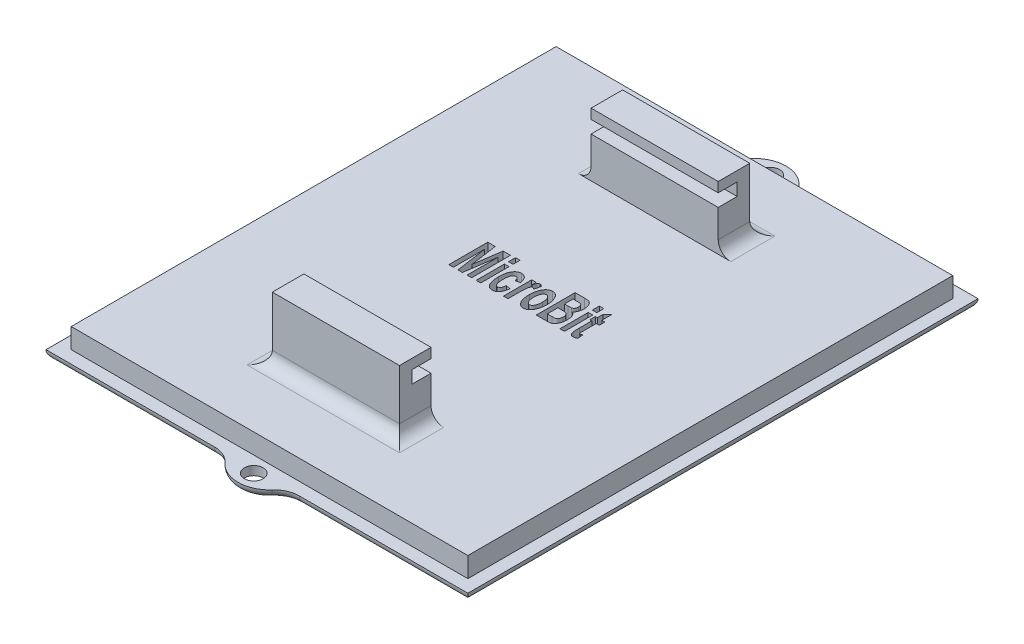
SolidWorks part; units mm, degrees
ref_plane "Front Plane" through (0, 0, 0) normal (0, 0, 1) x (1, 0, 0)
ref_plane "Top Plane" through (0, 0, 0) normal (0, 1, 0) x (1, 0, 0)
ref_plane "Right Plane" through (0, 0, 0) normal (1, 0, 0) x (0, 0, -1)
sketch "Sketch1" plane through (0, 0, 0) normal (0, 1, 0) x (1, 0, 0)
  line L0 (-31.45, 38.45) -> (31.45, 38.45)
  line L5 (-31.45, 38.45) -> (-31.45, -38.45)
  line L6 (-31.45, -38.45) -> (31.45, -38.45)
  line L7 (31.45, 38.45) -> (31.45, -38.45)
  point P11 (-31.45, 0)
  point P12 (0, -38.45)
  dimension "D3" = 76.9
  dimension "D4" = 62.9
extrude "Boss-Extrude1" add sketch "Sketch1" along normal blind 4.575
sketch "Sketch11" plane through (0, 0, 0) normal (0, -1, 0) x (-1, 0, 0)
  line L0 (-31.45, 38.45) -> (31.45, 38.45) construction
  line L1 (-33.45, -40.45) -> (33.45, -40.45)
  line L2 (-33.45, -40.45) -> (-33.45, 40.45)
  line L3 (-33.45, 40.45) -> (33.45, 40.45)
  line L4 (33.45, -40.45) -> (33.45, 40.45)
  line L5 (-31.45, -38.45) -> (-31.45, 38.45) construction
  line L6 (31.45, -38.45) -> (-31.45, -38.45) construction
  line L13 (31.45, 38.45) -> (31.45, -38.45) construction
  dimension "D1" = 2
  dimension "D2" = 2
  dimension "D3" = 2
  dimension "D4" = 2
extrude "Boss-Extrude5" add sketch "Sketch11" against normal blind 1.4
sketch "Sketch4" plane through (0, 0, 0) normal (0, 1, 0) x (1, 0, 0)
  line L2 (-31.45, -38.45) -> (31.45, -38.45) construction
  line L3 (33.45, -40.45) -> (-33.45, -40.45) construction
  line L5 (-6.7082, -40.45) -> (6.7082, -40.45)
  arc A3 (-6.7082, -40.45) -> (-3.7268, -41.7833) centre (-6.7082, -44.45) cw
  arc A4 (-3.7268, -41.7833) -> (3.7268, -41.7833) centre (0, -38.45) ccw
  arc A5 (3.7268, -41.7833) -> (6.7082, -40.45) centre (6.7082, -44.45) cw
  dimension "D1" = 5
  dimension "D4" = 4
extrude "Boss-Extrude3" add sketch "Sketch4" along normal blind 1.4
sketch "Sketch12" plane through (0, 1.4, 0) normal (0, 1, 0) x (1, 0, 0)
  line L0 (0, -38.45) -> (0, -43.45) construction
  line L1 (-31.45, -38.45) -> (31.45, -38.45) construction
  arc A0 (-3.7268, -41.7833) -> (3.7268, -41.7833) centre (0, -38.45) ccw construction
  circle A1 centre (0, -40.95) radius 1.5
  dimension "D1" = 3
extrude "Cut-Extrude3" cut sketch "Sketch12" against normal up to next
mirror "Mirror1" about plane through (0, 0, 0) normal (0, 0, 1) of "Cut-Extrude3", "Boss-Extrude3"
fillet "Fillet1" radius 1.4 12 edges at (20.0791, 0, -40.45) (5.0752, 0, -40.7985) (0, 0, -43.45) (-5.0752, 0, -40.7985) (-20.0791, 0, -40.45) (-33.45, 0, 0) (-20.0791, 0, 40.45) (-5.0752, 0, 40.7985) (0, 0, 43.45) (5.0752, 0, 40.7985) (20.0791, 0, 40.45) (33.45, 0, 0)
sketch "Sketch5" plane through (0, 4.575, 0) normal (0, 1, 0) x (1, 0, 0)
  line L0 (-15, 0) -> (15, 0) construction
  text T0 "MicroBit" font "Arial Narrow" height in points 24
  point P6 (0, 0)
  dimension "D1" = 30
extrude "Letters" cut sketch "Sketch5" against normal blind 2
sketch "Sketch21" plane through (0, 4.575, 0) normal (0, 1, 0) x (1, 0, 0)
  line L1 (-21.1498, 24.9347) -> (20.8502, 24.9347)
  line L2 (-21.1498, 24.9347) -> (-21.1498, -26.5653)
  line L3 (-21.1498, -26.5653) -> (20.8502, -26.5653)
  line L4 (20.8502, 24.9347) -> (20.8502, -26.5653)
  line L5 (-21.1498, 24.9347) -> (20.8502, -26.5653) construction
  line L6 (-21.1498, -26.5653) -> (20.8502, 24.9347) construction
  line L7 (-10.2291, -22.7722) -> (9.9294, -22.7722)
  line L8 (-10.2291, -22.7722) -> (-10.2291, -27.7722)
  line L9 (-10.2291, -27.7722) -> (9.9294, -27.7722)
  line L10 (9.9294, -22.7722) -> (9.9294, -27.7722)
  line L11 (-10.2291, -22.7722) -> (9.9294, -27.7722) construction
  line L12 (-10.2291, -27.7722) -> (9.9294, -22.7722) construction
  point P4 (-0.1498, -0.8153)
  point P9 (-0.1498, -25.2722)
  dimension "D1" = 42
  dimension "D2" = 51.5
  dimension "D3" = 5
extrude "Boss-Extrude8" add sketch "Sketch21" along normal blind 10 contours L9 L10 L7 L8
sketch "Sketch33" plane through (9.9294, 0, 0) normal (1, 0, 0) x (0, 0, -1)
  line L0 (-22.7722, 14.575) -> (-22.7722, 4.575) construction
  line L1 (-22.7722, 13.0159) -> (-25.7722, 13.0159)
  line L2 (-22.7722, 13.0159) -> (-22.7722, 11.0159)
  line L3 (-22.7722, 11.0159) -> (-25.7722, 11.0159)
  line L4 (-25.7722, 13.0159) -> (-25.7722, 11.0159)
  line L5 (-22.7722, 13.0159) -> (-25.7722, 11.0159) construction
  line L6 (-22.7722, 11.0159) -> (-25.7722, 13.0159) construction
  point P4 (-24.2722, 12.0159)
  dimension "D1" = 2
  dimension "D2" = 3
extrude "Cut-Extrude7" cut sketch "Sketch33" against normal blind 25
mirror "Mirror2" about plane through (0, 0, 0) normal (0, 0, 1) of "Boss-Extrude8", "Cut-Extrude7"
fillet "Fillet2" radius 2 6 edges at (9.9294, 4.575, 25.2722) (-10.2291, 4.575, 25.2722) (-0.1498, 4.575, 27.7722) (-10.2291, 4.575, -25.2722) (-0.1498, 4.575, -27.7722) (9.9294, 4.575, -25.2722)
